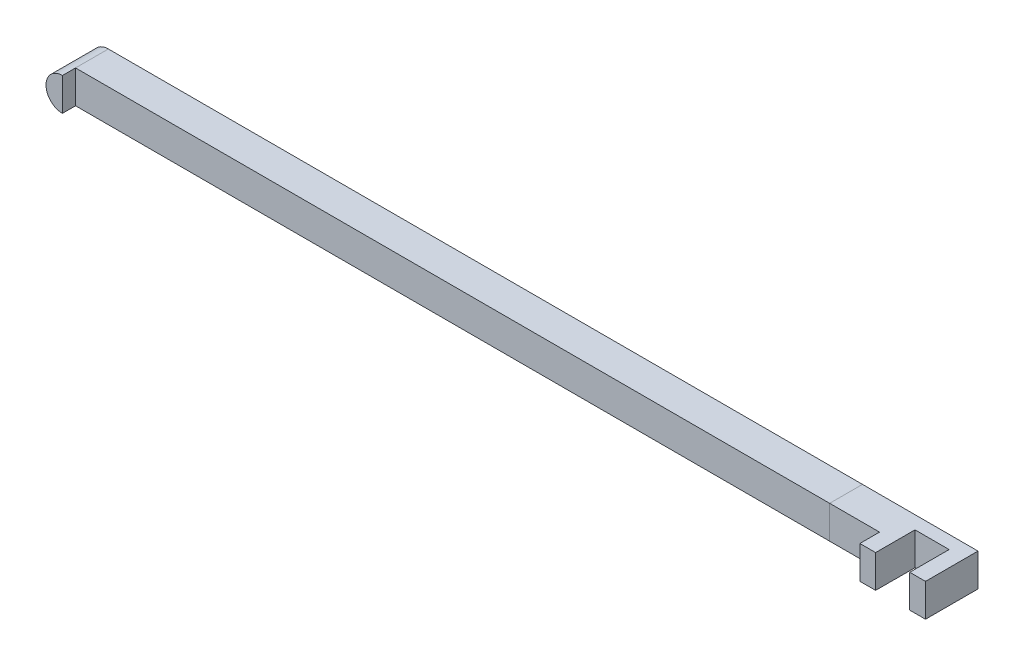
SolidWorks part; units mm, degrees
ref_plane "Front Plane" through (0, 0, 0) normal (1, 0, 0) x (0, 1, 0)
ref_plane "Top Plane" through (0, 0, 0) normal (0, 0, 1) x (0, 1, 0)
ref_plane "Right Plane" through (0, 0, 0) normal (0, 1, 0) x (-1, 0, 0)
sketch "Sketch1" plane through (0, 0, 0) normal (0, 1, 0) x (-1, 0, 0)
  line L1 (-62.5, -2.5) -> (62.5, -2.5)
  line L2 (-62.5, -2.5) -> (-62.5, 2.5)
  line L3 (-62.5, 2.5) -> (62.5, 2.5)
  line L4 (62.5, -2.5) -> (62.5, 2.5)
  line L5 (-62.5, -2.5) -> (62.5, 2.5) construction
  line L6 (-62.5, 2.5) -> (62.5, -2.5) construction
  point P0 (0, 0)
  dimension "D1" = 125
  dimension "D2" = 5
extrude "Boss-Extrude1" add sketch "Sketch1" along normal blind 5
fillet "Fillet1" radius 2.5 2 edges at (-62.5, 5, 0) (-62.5, 0, 0)
sketch "Sketch3" plane through (62.5, 0, 0) normal (1, 0, 0) x (0, 1, 0)
  line L7 (5, 2.5) -> (0, 2.5) construction
  line L8 (0, 2.5) -> (5, 2.5)
  line L9 (0, 2.5) -> (0, -2.5)
  line L10 (0, -2.5) -> (5, -2.5)
  line L11 (5, 2.5) -> (5, -2.5)
  line L12 (5, -2.5) -> (0, -2.5) construction
  line L14 (5, 2.5) -> (5, -2.5) construction
  dimension "D1" = 5
extrude "Boss-Extrude2" add sketch "Sketch3" along normal blind 10
sketch "Sketch4" plane through (0, 0, 2.5) normal (0, 0, 1) x (1, 0, 0)
  line L0 (72.5, 5) -> (-60, 5) construction
  line L1 (64.9, 5) -> (70.1, 5)
  line L2 (64.9, 5) -> (64.9, 0)
  line L3 (64.9, 0) -> (70.1, 0)
  line L4 (70.1, 5) -> (70.1, 0)
  line L5 (72.5, 0) -> (-60, 0) construction
  line L6 (72.5, 5) -> (72.5, 0) construction
  line L7 (35, 5) -> (35, 4) construction
  dimension "D1" = 5.2
  dimension "D2" = 2.4
  dimension "D3" = 29.9
extrude "Cut-Extrude1" cut sketch "Sketch4" against normal blind 3 contours L2 L3 L4 L1
sketch "Sketch5" plane through (0, 0, 2.5) normal (0, 0, 1) x (1, 0, 0)
  line L0 (-60, 0) -> (-60, 5)
  arc A0 (-60, 5) -> (-60, 0) centre (-60, 2.5) ccw
  arc A1 (-62.5, 2.5) -> (-60, 0) centre (-60, 2.5) ccw construction
  dimension "D1" = 0
extrude "Boss-Extrude3" add sketch "Sketch5" along normal blind 2
sketch "Sketch6" plane through (0, 0, 2.5) normal (0, 0, 1) x (1, 0, 0)
  line L0 (54.9, 5) -> (54.9, 0)
  line L5 (-60, 5) -> (64.9, 5) construction
  line L6 (-60, 0) -> (64.9, 0) construction
  line L7 (64.9, 5) -> (64.9, 0) construction
  dimension "D1" = 10
sketch "Sketch7" plane through (0, 0, 2.5) normal (0, 0, 1) x (1, 0, 0)
  line L0 (62.5, 5) -> (64.9, 5)
  line L1 (70.1, 5) -> (72.5, 5)
  line L2 (70.1, 5) -> (70.1, 0)
  line L3 (70.1, 0) -> (72.5, 0)
  line L4 (72.5, 5) -> (72.5, 0)
  line L5 (62.5, 5) -> (62.5, 0.0086)
  line L6 (62.5, 0.0086) -> (64.9, 0.0086)
  line L7 (64.9, 5) -> (64.9, 0.0086)
  line L9 (64.9, 0) -> (70.1, 0) construction
  dimension "D1" = 5
  dimension "D2" = 2.4
  dimension "D3" = 5
  dimension "D4" = 2.4
extrude "Boss-Extrude4" add sketch "Sketch7" along normal blind 3
split "Split1" trim tools "Sketch6" bodies to split 115 resulting bodies 113 114
